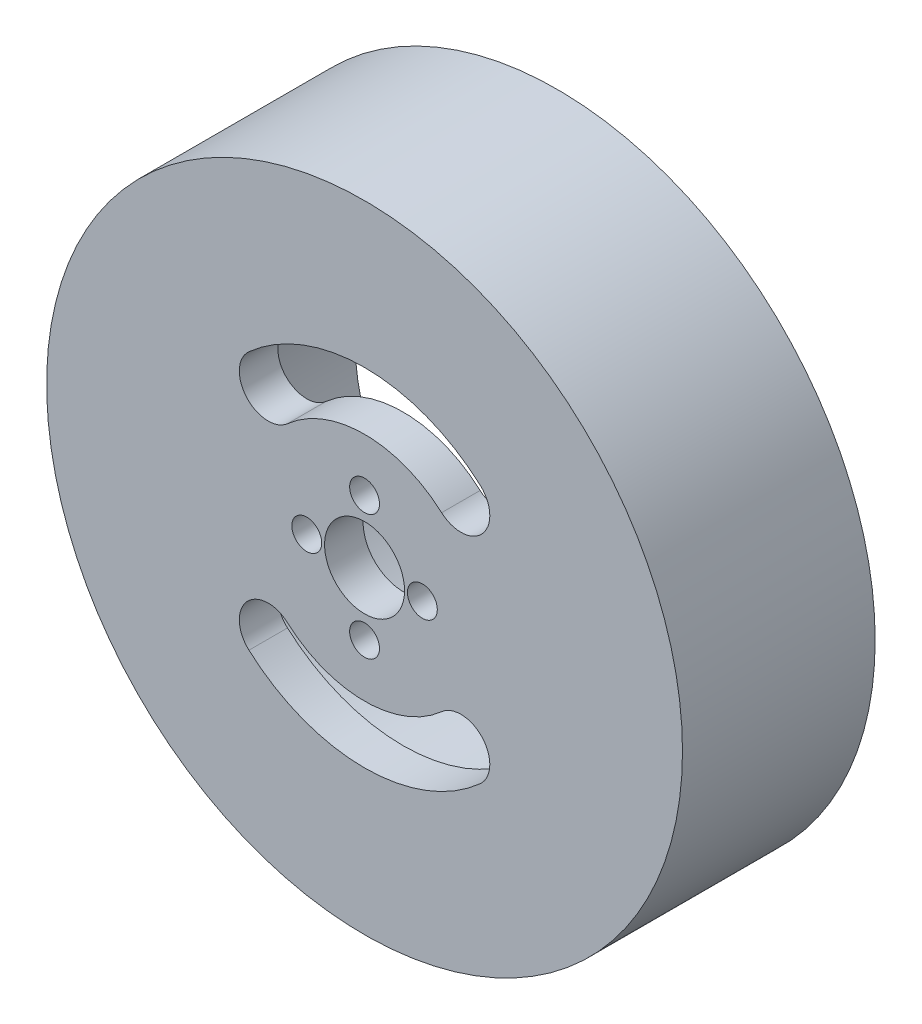
SolidWorks part; units mm, degrees
ref_plane "前视基准面" through (0, 0, 0) normal (0, 0, 1) x (1, 0, 0)
ref_plane "上视基准面" through (0, 0, 0) normal (0, 1, 0) x (1, 0, 0)
ref_plane "右视基准面" through (0, 0, 0) normal (1, 0, 0) x (0, 0, -1)
sketch "草图1" plane through (0, 0, 0) normal (0, 0, 1) x (1, 0, 0)
  circle A0 centre (0, 0) radius 33
  circle A1 centre (0, 0) radius 40
  arc A2 (0, 8.05) -> (0, 4.95) centre (0, 6.5) ccw
  arc A3 (0, 4.95) -> (0, 8.05) centre (0, 6.5) ccw
  arc A4 (0, 8.05) -> (0, 4.95) centre (0, 6.5) ccw
  arc A5 (0, 4.95) -> (0, 8.05) centre (0, 6.5) ccw
  arc A6 (-8, -8.9443) -> (-10, -8.1803) centre (-10, -11.1803) ccw
  arc A7 (-8, -8.9443) -> (8, -8.9443) centre (0, 0) ccw
  arc A8 (10, -8.1803) -> (8, -8.9443) centre (10, -11.1803) ccw
  arc A9 (12, -13.4164) -> (10, -8.1803) centre (10, -11.1803) ccw
  arc A10 (-12, -13.4164) -> (12, -13.4164) centre (0, 0) ccw
  arc A11 (-10, -8.1803) -> (-12, -13.4164) centre (-10, -11.1803) ccw
  arc A12 (-8, -8.9443) -> (-10, -8.1803) centre (-10, -11.1803) ccw
  arc A13 (-8, -8.9443) -> (8, -8.9443) centre (0, 0) ccw
  arc A14 (10, -8.1803) -> (8, -8.9443) centre (10, -11.1803) ccw
  arc A15 (12, -13.4164) -> (10, -8.1803) centre (10, -11.1803) ccw
  arc A16 (-12, -13.4164) -> (12, -13.4164) centre (0, 0) ccw
  arc A17 (-10, -8.1803) -> (-12, -13.4164) centre (-10, -11.1803) ccw
  arc A18 (-12, 13.4164) -> (-8, 8.9443) centre (-10, 11.1803) ccw
  arc A19 (0, 18) -> (-12, 13.4164) centre (0, 0) ccw
  arc A20 (12, 13.4164) -> (0, 18) centre (0, 0) ccw
  arc A21 (8, 8.9443) -> (12, 13.4164) centre (10, 11.1803) ccw
  arc A22 (8, 8.9443) -> (0, 12) centre (0, 0) ccw
  arc A23 (0, 12) -> (-8, 8.9443) centre (0, 0) ccw
  arc A24 (-12, 13.4164) -> (-8, 8.9443) centre (-10, 11.1803) ccw
  arc A25 (0, 18) -> (-12, 13.4164) centre (0, 0) ccw
  arc A26 (12, 13.4164) -> (0, 18) centre (0, 0) ccw
  arc A27 (8, 8.9443) -> (12, 13.4164) centre (10, 11.1803) ccw
  arc A28 (8, 8.9443) -> (0, 12) centre (0, 0) ccw
  arc A29 (0, 12) -> (-8, 8.9443) centre (0, 0) ccw
  arc A30 (0, -4.95) -> (0, -8.05) centre (0, -6.5) ccw
  arc A31 (0, -8.05) -> (0, -4.95) centre (0, -6.5) ccw
  arc A32 (0, -4.95) -> (0, -8.05) centre (0, -6.5) ccw
  arc A33 (0, -8.05) -> (0, -4.95) centre (0, -6.5) ccw
  arc A34 (6, 1.55) -> (6, -1.55) centre (6, 0) ccw
  arc A35 (6, -1.55) -> (6, 1.55) centre (6, 0) ccw
  arc A36 (6, 1.55) -> (6, -1.55) centre (6, 0) ccw
  arc A37 (6, -1.55) -> (6, 1.55) centre (6, 0) ccw
  arc A38 (-6, 1.55) -> (-6, -1.55) centre (-6, 0) ccw
  arc A39 (-6, -1.55) -> (-6, 1.55) centre (-6, 0) ccw
  arc A40 (-6, 1.55) -> (-6, -1.55) centre (-6, 0) ccw
  arc A41 (-6, -1.55) -> (-6, 1.55) centre (-6, 0) ccw
  arc A42 (0, 4.15) -> (0, -4.15) centre (0, 0) ccw
  arc A43 (0, -4.15) -> (0, 4.15) centre (0, 0) ccw
  arc A44 (0, 4.15) -> (0, -4.15) centre (0, 0) ccw
  arc A45 (0, -4.15) -> (0, 4.15) centre (0, 0) ccw
  circle A46 centre (0, 0) radius 21
  dimension "D8" = 66
  dimension "D9" = 80
  dimension "D10" = 42
  dimension "D1" = 0
  dimension "D2" = 0
  dimension "D3" = 0
  dimension "D4" = 0
  dimension "D5" = 0
  dimension "D6" = 0
  dimension "D7" = 0
extrude "凸台-拉伸1" add sketch "草图1" along normal blind 20 contours A0
extrude "切除-拉伸2" cut sketch "草图1<5>" against normal mid plane 50 contours A28 A29 A24 A25 A26 A27 | A13 A14 A15 A16 A17 A12
sketch "草图1<5>" plane through (0, 0, 0) normal (0, 0, 1) x (1, 0, 0) same geometry as "草图1"
extrude "切除-拉伸3" cut sketch "草图1<6>" along normal blind 16 contours A46
sketch "草图1<6>" plane through (0, 0, 0) normal (0, 0, 1) x (1, 0, 0) same geometry as "草图1"
extrude "切除-拉伸5" cut sketch "草图1<7>" against normal mid plane 60 contours A40 A41 | A33 A32 | A45 A44 | A37 A36 | A4 A5
sketch "草图1<7>" plane through (0, 0, 0) normal (0, 0, 1) x (1, 0, 0) same geometry as "草图1"
